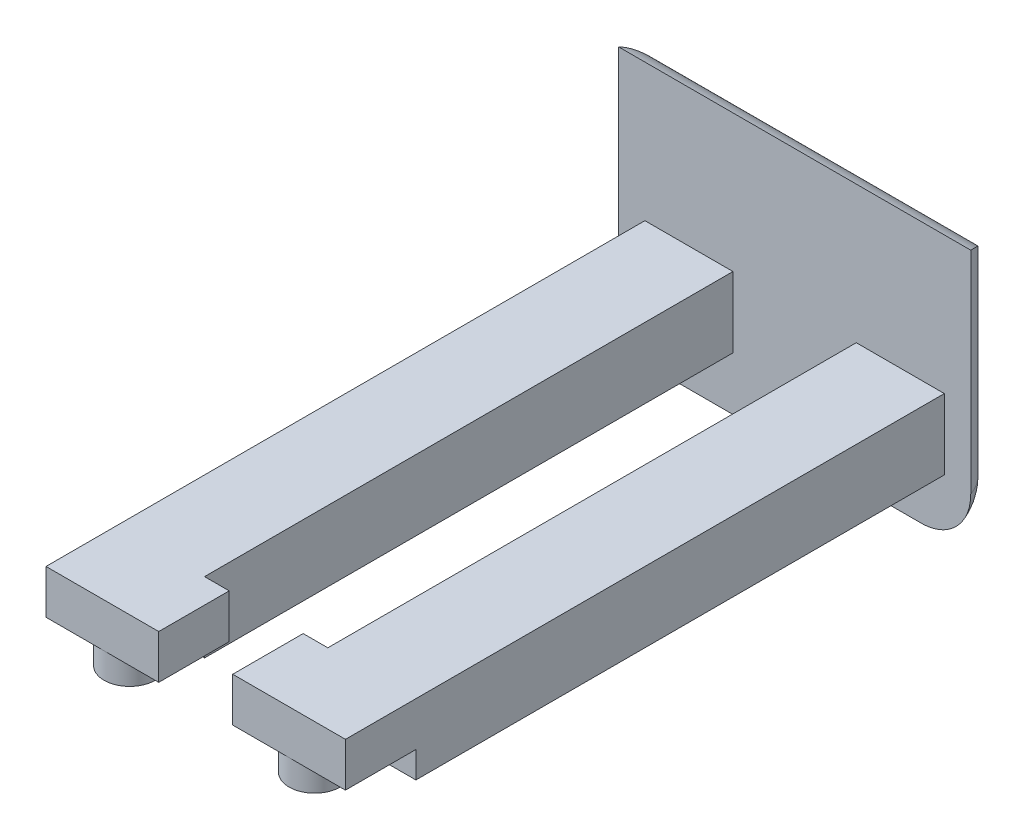
SolidWorks part; units mm, degrees
ref_plane "Front Plane" through (0, 0, 0) normal (0, 0, 1) x (1, 0, 0)
ref_plane "Top Plane" through (0, 0, 0) normal (0, 1, 0) x (1, 0, 0)
ref_plane "Right Plane" through (0, 0, 0) normal (1, 0, 0) x (0, 0, -1)
sketch "Sketch1" plane through (0, 0, 0) normal (0, 0, 1) x (1, 0, 0)
  line L1 (25.4, -19.05) -> (-25.4, -19.05)
  line L2 (25.4, -19.05) -> (25.4, 19.05)
  line L3 (25.4, 19.05) -> (-25.4, 19.05)
  line L4 (-25.4, -19.05) -> (-25.4, 19.05)
  line L5 (25.4, -19.05) -> (-25.4, 19.05) construction
  line L6 (25.4, 19.05) -> (-25.4, -19.05) construction
  point P0 (0, 0)
  dimension "D1" = 50.8
  dimension "D2" = 38.1
extrude "Boss-Extrude1" add sketch "Sketch1" along normal blind 5.08
sketch "Sketch2" plane through (0, 0, 5.08) normal (0, 0, 1) x (1, 0, 0)
  line L1 (-21.59, -0.762) -> (-5.08, -0.762)
  line L2 (-21.59, -0.762) -> (-21.59, -10.922)
  line L3 (-21.59, -10.922) -> (-5.08, -10.922)
  line L4 (-5.08, -0.762) -> (-5.08, -10.922)
  line L5 (5.08, -0.762) -> (21.59, -0.762)
  line L6 (5.08, -0.762) -> (5.08, -10.922)
  line L7 (5.08, -10.922) -> (21.59, -10.922)
  line L8 (21.59, -0.762) -> (21.59, -10.922)
  dimension "D1" = 10.16
  dimension "D2" = 19.812
  dimension "D3" = 10.16
  dimension "D4" = 3.81
  dimension "D5" = 3.81
extrude "Boss-Extrude2" add sketch "Sketch2" along normal blind 76.2
sketch "Sketch3" plane through (0, 0, 81.28) normal (0, 0, 1) x (1, 0, 0)
  line L0 (-21.59, -10.922) -> (-5.08, -10.922) construction
  line L1 (-5.08, -0.762) -> (-8.89, -0.762)
  line L2 (-5.08, -0.762) -> (-5.08, -10.922)
  line L3 (-5.08, -10.922) -> (-8.89, -10.922)
  line L4 (-8.89, -0.762) -> (-8.89, -10.922)
  line L5 (5.08, -10.922) -> (21.59, -10.922) construction
  line L6 (5.08, -0.762) -> (8.89, -0.762)
  line L7 (5.08, -0.762) -> (5.08, -10.922)
  line L8 (5.08, -10.922) -> (8.89, -10.922)
  line L9 (8.89, -0.762) -> (8.89, -10.922)
  dimension "D1" = 3.81
  dimension "D2" = 3.81
extrude "Cut-Extrude1" cut sketch "Sketch3" against normal up to surface (76.2 mm away) up to face at (0, 0, 5.08)
sketch "Sketch4" plane through (0, 0, 81.28) normal (0, 0, 1) x (1, 0, 0)
  line L0 (8.89, -10.922) -> (21.59, -10.922) construction
  line L1 (-21.59, -0.762) -> (-5.08, -0.762)
  line L2 (-21.59, -0.762) -> (-21.59, -10.922)
  line L3 (-21.59, -10.922) -> (-5.08, -10.922)
  line L4 (-5.08, -0.762) -> (-5.08, -10.922)
  line L5 (21.59, -0.762) -> (5.08, -0.762)
  line L6 (21.59, -0.762) -> (21.59, -10.922)
  line L7 (21.59, -10.922) -> (5.08, -10.922)
  line L8 (5.08, -0.762) -> (5.08, -10.922)
  dimension "D1" = 16.51
  dimension "D2" = 16.51
extrude "Boss-Extrude3" add sketch "Sketch4" along normal blind 12.7
sketch "Sketch6" plane through (0, -10.922, 0) normal (0, -1, 0) x (1, 0, 0)
  line L1 (-5.08, 81.28) -> (-21.59, 81.28)
  line L2 (-5.08, 81.28) -> (-5.08, 93.98)
  line L3 (-5.08, 93.98) -> (-21.59, 93.98)
  line L4 (-21.59, 81.28) -> (-21.59, 93.98)
  line L5 (5.08, 81.28) -> (21.59, 81.28)
  line L6 (5.08, 81.28) -> (5.08, 93.98)
  line L7 (5.08, 93.98) -> (21.59, 93.98)
  line L8 (21.59, 81.28) -> (21.59, 93.98)
extrude "Cut-Extrude2" cut sketch "Sketch6" against normal blind 3.81
sketch "Sketch5" plane through (0, -10.922, 0) normal (0, -1, 0) x (1, 0, 0)
  line L0 (-5.08, 87.63) -> (-21.59, 87.63) construction
  line L1 (-5.08, 93.98) -> (-5.08, 81.28) construction
  line L2 (-21.59, 81.28) -> (-21.59, 5.08) construction
  line L3 (5.08, 87.63) -> (21.59, 87.63) construction
  line L4 (5.08, 93.98) -> (5.08, 81.28) construction
  line L5 (21.59, 81.28) -> (21.59, 5.08) construction
  circle A0 centre (-13.335, 87.63) radius 3.683
  circle A1 centre (13.335, 87.63) radius 3.683
  dimension "D1" = 7.366
  dimension "D2" = 7.366
extrude "Boss-Extrude4" add sketch "Sketch5" against normal blind 3.81
fillet "Fillet1" radius 7.62 1 edges at (0, 19.05, 0)
fillet "Fillet4" radius 7.62 2 edges at (-25.4, -3.5921, 0) (25.4, -3.5921, 0)
fillet "Fillet7" radius 7.62 3 edges at (-22.6152, -19.05, 1.3983) (22.6152, -19.05, 1.3983) (0, -19.05, 0)
sketch "Sketch7" plane through (0, 0, 93.98) normal (0, 0, 1) x (1, 0, 0)
  line L1 (-21.59, -0.762) -> (-5.08, -0.762)
  line L2 (-21.59, -0.762) -> (-21.59, -7.112)
  line L3 (-21.59, -7.112) -> (-5.08, -7.112)
  line L4 (-5.08, -0.762) -> (-5.08, -7.112)
  line L5 (5.08, -0.762) -> (21.59, -0.762)
  line L6 (5.08, -0.762) -> (5.08, -7.112)
  line L7 (5.08, -7.112) -> (21.59, -7.112)
  line L8 (21.59, -0.762) -> (21.59, -7.112)
extrude "ledge-reduction" cut sketch "Sketch7" against normal blind 2.54
sketch "Sketch8" plane through (5.08, 0, 0) normal (-1, 0, 0) x (0, 0, 1)
  line L1 (81.28, -0.762) -> (91.44, -0.762)
  line L2 (81.28, -0.762) -> (81.28, -7.112)
  line L3 (81.28, -7.112) -> (91.44, -7.112)
  line L4 (91.44, -0.762) -> (91.44, -7.112)
extrude "Cut-Extrude4" cut sketch "Sketch8" against normal blind 0.254
sketch "Sketch9" plane through (-5.08, 0, 0) normal (1, 0, 0) x (0, 0, -1)
  line L1 (-91.44, -0.762) -> (-81.28, -0.762)
  line L2 (-91.44, -0.762) -> (-91.44, -7.112)
  line L3 (-91.44, -7.112) -> (-81.28, -7.112)
  line L4 (-81.28, -0.762) -> (-81.28, -7.112)
extrude "Cut-Extrude5" cut sketch "Sketch9" against normal blind 0.254
ref_plane "Plane1" through (-8.89, -0.762, 81.28) normal (0, 0, 1) x (1, 0, 0)
equation "\"D5@Sketch2\"=\"D4@Sketch2\""
equation "\"D2@Sketch4\"=\"D1@Sketch4\""
equation "\"D2@Sketch5\"=\"D1@Sketch5\""
